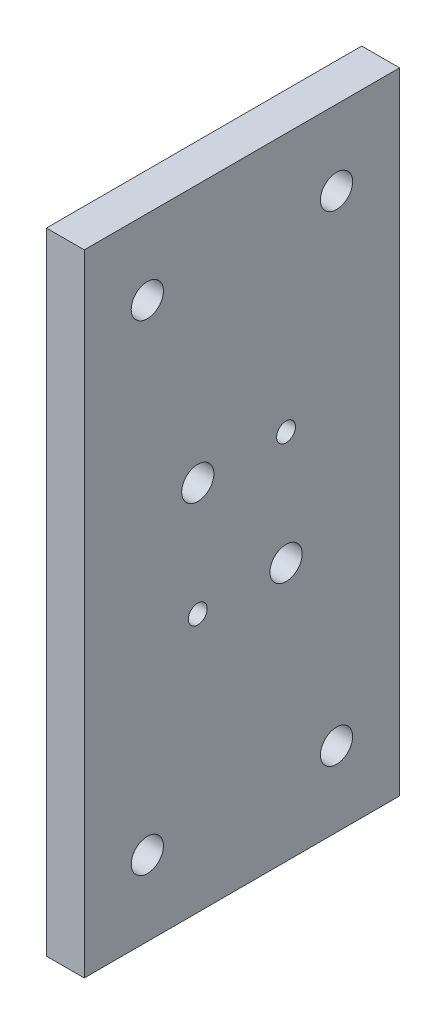
SolidWorks part; units mm, degrees
ref_plane "Front Plane" through (0, 0, 0) normal (1, 0, 0) x (0, 1, 0)
ref_plane "Top Plane" through (0, 0, 0) normal (0, 0, 1) x (0, 1, 0)
ref_plane "Right Plane" through (0, 0, 0) normal (0, 1, 0) x (-1, 0, 0)
sketch "Sketch1" plane through (0, 0, 0) normal (1, 0, 0) x (0, 1, 0)
  line L0 (0, 25) -> (0, -25) construction
  line L1 (-50, -25) -> (50, -25)
  line L2 (-50, -25) -> (-50, 25)
  line L3 (-50, 25) -> (50, 25)
  line L4 (50, -25) -> (50, 25)
  line L5 (-50, -25) -> (50, 25) construction
  line L6 (-50, 25) -> (50, -25) construction
  line L8 (-9, -7) -> (9, -7) construction
  line L9 (-9, -7) -> (-9, 7) construction
  line L10 (-9, 7) -> (9, 7) construction
  line L11 (9, -7) -> (9, 7) construction
  line L12 (-9, -7) -> (9, 7) construction
  line L13 (-9, 7) -> (9, -7) construction
  line L14 (-38.1, -15) -> (38.1, -15) construction
  line L15 (-38.1, -15) -> (-38.1, 15) construction
  line L16 (-38.1, 15) -> (38.1, 15) construction
  line L17 (38.1, -15) -> (38.1, 15) construction
  line L18 (-38.1, -15) -> (38.1, 15) construction
  line L19 (-38.1, 15) -> (38.1, -15) construction
  circle A0 centre (-9, 7) radius 1.5
  circle A1 centre (-9, -7) radius 2.555
  circle A2 centre (9, -7) radius 1.5
  circle A3 centre (9, 7) radius 2.555
  circle A4 centre (-38.1, 15) radius 2.555
  circle A5 centre (-38.1, -15) radius 2.555
  circle A6 centre (38.1, 15) radius 2.555
  circle A7 centre (38.1, -15) radius 2.555
  point P0 (0, 0)
  point P8 (0, 0)
  point P17 (0, 0)
  dimension "D5" = 5.11
  dimension "D6" = 3
  dimension "D9" = 5.11
  dimension "D10" = 5.11
  dimension "D11" = 5.11
  dimension "D12" = 3
  dimension "D13" = 3
  dimension "D1" = 14
  dimension "D2" = 18
  dimension "D3" = 100
  dimension "D4" = 50
  dimension "D7" = 76.2
  dimension "D8" = 30
extrude "Boss-Extrude1" add sketch "Sketch1" along normal blind 6
